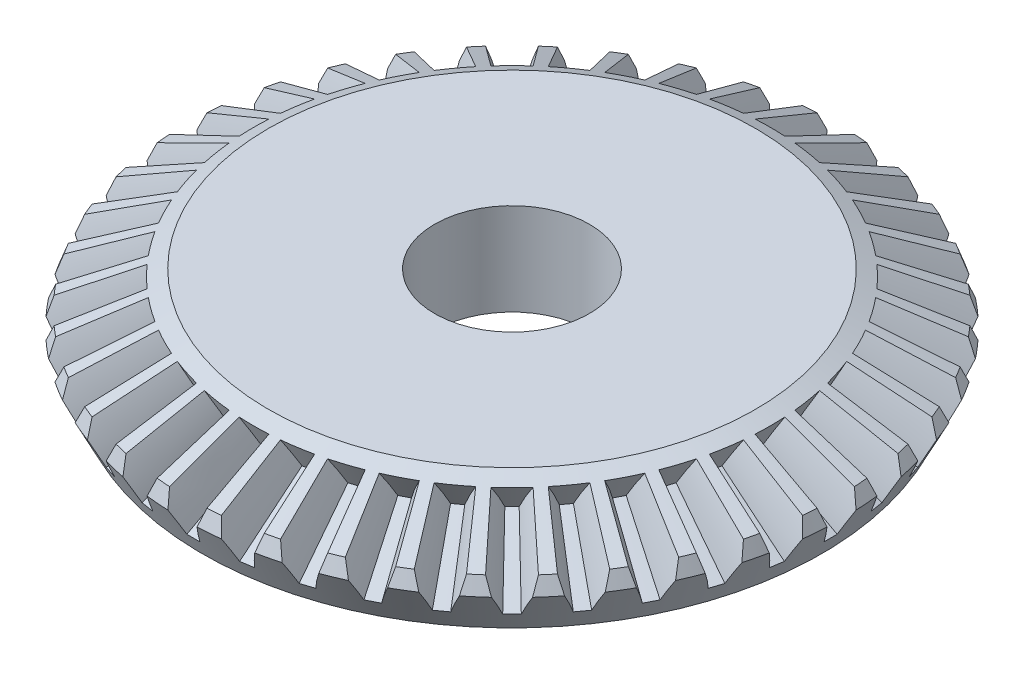
SolidWorks part; units mm, degrees
note: The reader was unsure of these and kept them because the rebuilt part matched: shared geometry of "Section Profile<5>".
ref_plane "Front Plane" through (0, 0, 0) normal (0, 0, 1) x (1, 0, 0)
ref_plane "Top Plane" through (0, 0, 0) normal (0, 1, 0) x (1, 0, 0)
ref_plane "Right Plane" through (0, 0, 0) normal (1, 0, 0) x (0, 0, -1)
ref_plane "Center Plane" through (0, 0, 0) normal (0, 0, 1) x (1, 0, 0)
sketch "Section Profile" plane through (0, 0, 0) normal (0, 0, 1) x (1, 0, 0)
  line L0 (0, 0) -> (0, -63.5) construction
  line L1 (-6, -15.5398) -> (-23.9801, -15.5398)
  line L2 (-23.9801, -15.5398) -> (-25.968, -11.5641)
  line L3 (-25.968, -11.5641) -> (-18.864, -8.4005)
  line L4 (-18.864, -8.4005) -> (-6, -8.4005)
  line L5 (-6, -8.4005) -> (-6, -15.5398)
  line L6 (-25.4, -12.7) -> (-19.5862, -9.7931) construction
  line L7 (-20.0242, -8.9172) -> (-18.9293, -11.107)
  line L8 (-18.9293, -11.107) -> (-24.5481, -14.4039) construction
  line L9 (-18.9293, -11.107) -> (-6, -11.107)
  line L10 (-25.5571, -12.3859) -> (-25.1286, -11.1903)
  line L11 (-25.968, -11.5641) -> (-25.3429, -11.7881) construction
  line L12 (0, 0) -> (-31.75, 0) construction
  dimension "D2" = 6
  dimension "D3" = 1.27
  dimension "D4" = 1.905
  dimension "D6" = 25.4
  dimension "D7" = 1.27
  dimension "D8" = 6.5
  dimension "D9" = 1.27
  dimension "D10" = 1.27
  dimension "D11" = 90
  dimension "D5" = 12.7
revolve "Revolve1" add sketch "Section Profile" angle 360 about L0
ref_plane "Tooth Plane" through (-25.4, -12.7, 0) normal (0.8944, 0.4472, 0) x (-0.4472, 0.8944, 0)
sketch "Tooth Profile" plane through (-25.4, -12.7, 0) normal (0.8944, 0.4472, 0) x (-0.4472, 0.8944, 0)
  line L0 (-56.7961, 0) -> (-3.4257, -0.2154)
  line L1 (-56.7961, 0) -> (-3.4257, 0.2154)
  line L2 (-56.7961, 0) -> (1.27, 0) construction
  line L3 (-0.0088, -0.9974) -> (-56.7961, 0) construction
  line L4 (-56.7961, 0) -> (-0.0088, 0.9974) construction
  circle A0 centre (-56.7961, 0) radius 58.0661 construction
  circle A1 centre (-56.7961, 0) radius 53.3709 construction
  circle A2 centre (-56.7961, 0) radius 56.7961 construction
  arc A3 (1.3762, -1.554) -> (1.3762, 1.554) centre (-56.7961, 0) ccw
  circle A4 centre (-56.7961, 0) radius 55.2086
  spline S0 degree 4 poles (-3.4257, -0.2154) (-3.3862, -0.2155) (-3.2755, -0.2186) (-3.0666, -0.2345) (-2.7269, -0.275) (-2.099, -0.381) (-1.3532, -0.559) (-0.5213, -0.8095) (0.3598, -1.1274) (1.1043, -1.4294) (1.8376, -1.7578) (2.5596, -2.1103) (3.4221, -2.5648) (4.4411, -3.1515) (5.6034, -3.89) (6.8927, -4.7992) (8.1622, -5.7851) (9.3878, -6.824) (10.4229, -7.7768) (11.2824, -8.6199) (11.9826, -9.3425) (12.5292, -9.9263) (13.2058, -10.6779) (13.8538, -11.4281) (14.5026, -12.2204) (15.2306, -13.1426) (15.8643, -13.9908) (16.3987, -14.7279) (17.1314, -15.7961) (17.4562, -16.2884) (17.9484, -17.0504) (18.1922, -17.4486) (18.4082, -17.7948) (18.5072, -17.9626) (18.6069, -18.1262) (18.6477, -18.1948) knots 0 0 0 0 0 0.005377 0.015084 0.028532 0.04661 0.092111 0.119476 0.146842 0.174209 0.201575 0.228941 0.256307 0.307035 0.361767 0.4165 0.471232 0.525964 0.580697 0.608063 0.635429 0.662795 0.690161 0.744894 0.77226 0.799626 0.854358 0.881725 0.909091 0.954545 0.965909 0.977273 0.988636 1 1 1 1 1 construction
  spline S1 degree 4 poles (-3.4257, -0.2154) (-3.3862, -0.2155) (-3.2755, -0.2186) (-3.0666, -0.2345) (-2.7269, -0.275) (-2.099, -0.381) (-1.3532, -0.559) (-0.5213, -0.8095) (0.3598, -1.1274) (1.1043, -1.4294) (1.8376, -1.7578) (2.5596, -2.1103) (3.4221, -2.5648) (4.4411, -3.1515) (5.6034, -3.89) (6.8927, -4.7992) (8.1622, -5.7851) (9.3878, -6.824) (10.4229, -7.7768) (11.2824, -8.6199) (11.9826, -9.3425) (12.5292, -9.9263) (13.2058, -10.6779) (13.8538, -11.4281) (14.5026, -12.2204) (15.2306, -13.1426) (15.8643, -13.9908) (16.3987, -14.7279) (16.9164, -15.4827) (17.1209, -15.7859) (17.2222, -15.9378) knots 0 0 0 0 0 0.005377 0.015084 0.028532 0.04661 0.092111 0.119476 0.146842 0.174209 0.201575 0.228941 0.256307 0.307035 0.361767 0.4165 0.471232 0.525964 0.580697 0.608063 0.635429 0.662795 0.690161 0.744894 0.77226 0.799626 0.854358 0.881725 0.909091 0.909091 0.909091 0.909091 0.909091
  spline S2 degree 4 poles (-3.4257, 0.2154) (-3.3862, 0.2155) (-3.2755, 0.2186) (-3.0666, 0.2345) (-2.7269, 0.275) (-2.099, 0.381) (-1.3532, 0.559) (-0.5213, 0.8095) (0.3598, 1.1274) (1.1043, 1.4294) (1.8376, 1.7578) (2.5596, 2.1103) (3.4221, 2.5648) (4.4411, 3.1515) (5.6034, 3.89) (6.8927, 4.7992) (8.1622, 5.7851) (9.3878, 6.824) (10.4229, 7.7768) (11.2824, 8.6199) (11.9826, 9.3425) (12.5292, 9.9263) (13.2058, 10.6779) (13.8538, 11.4281) (14.5026, 12.2204) (15.2306, 13.1426) (15.8643, 13.9908) (16.3987, 14.7279) (17.1314, 15.7961) (17.4562, 16.2884) (17.9484, 17.0504) (18.1922, 17.4486) (18.4082, 17.7948) (18.5072, 17.9626) (18.6069, 18.1262) (18.6477, 18.1948) knots 0 0 0 0 0 0.005377 0.015084 0.028532 0.04661 0.092111 0.119476 0.146842 0.174209 0.201575 0.228941 0.256307 0.307035 0.361767 0.4165 0.471232 0.525964 0.580697 0.608063 0.635429 0.662795 0.690161 0.744894 0.77226 0.799626 0.854358 0.881725 0.909091 0.954545 0.965909 0.977273 0.988636 1 1 1 1 1 construction
  spline S3 degree 4 poles (-3.4257, 0.2154) (-3.3862, 0.2155) (-3.2755, 0.2186) (-3.0666, 0.2345) (-2.7269, 0.275) (-2.099, 0.381) (-1.3532, 0.559) (-0.5213, 0.8095) (0.3598, 1.1274) (1.1043, 1.4294) (1.8376, 1.7578) (2.5596, 2.1103) (3.4221, 2.5648) (4.4411, 3.1515) (5.6034, 3.89) (6.8927, 4.7992) (8.1622, 5.7851) (9.3878, 6.824) (10.4229, 7.7768) (11.2824, 8.6199) (11.9826, 9.3425) (12.5292, 9.9263) (13.2058, 10.6779) (13.8538, 11.4281) (14.5026, 12.2204) (15.2306, 13.1426) (15.8643, 13.9908) (16.3987, 14.7279) (16.9164, 15.4827) (17.1209, 15.7859) (17.2222, 15.9378) knots 0 0 0 0 0 0.005377 0.015084 0.028532 0.04661 0.092111 0.119476 0.146842 0.174209 0.201575 0.228941 0.256307 0.307035 0.361767 0.4165 0.471232 0.525964 0.580697 0.608063 0.635429 0.662795 0.690161 0.744894 0.77226 0.799626 0.854358 0.881725 0.909091 0.909091 0.909091 0.909091 0.909091
  dimension "D2" = 106.7418
  dimension "D4" = 110.4173
  dimension "D1" = 58.1931
  dimension "D6" = 113.5923
  dimension "D3" = 1.006
  dimension "D5" = 1.006
sketch "Center Point" plane through (0, 0, 0) normal (0, 0, 1) x (1, 0, 0)
  point P0 (0, 0)
loft "Cut-Loft1" cut profiles "Center Point" section "Center Point" section "Tooth Profile"
pattern_circular "CirPattern1" count 40 over 360 about axis through (0, 0, 0) along (0, -1, 0) of "Cut-Loft1"
revolve "Revolve2" add sketch "Section Profile<5>" angle 360 about L0
sketch "Section Profile<5>" plane through (0, 0, 0) normal (0, 0, 1) x (1, 0, 0) same geometry as "Section Profile"
equation "\"Module\"= 1.270mm'20dp = 1.270mod | 32dp = 0.7938mod"
equation "\"Teeth\"= 40"
equation "\"Meshing Teeth\"= 20"
equation "\"Pressure Angle\"= 20deg"
equation "\"Tooth Width\"= 6mm"
equation "\"Tooth Side Clearance\"= 0.5mm"
equation "\"D3@Section Profile\"=\"Module\""
equation "\"D4@Section Profile\"=1.5*\"Module\""
equation "\"D6@Section Profile\"=0.5 * \"Module\" * \"Teeth\""
equation "\"D8@Section Profile\"=\"Tooth Width\" + \"Tooth Side Clearance\""
equation "\"D2@Tooth Profile\" = \"D6@Tooth Profile\" * cos ( \"Pressure Angle\" ) "
equation "\"D3@Tooth Profile\" = 360 /  (  ( \"D6@Tooth Profile\" / \"Module\" )  * 4 ) "
equation "\"D4@Tooth Profile\" = \"D6@Tooth Profile\" -  ( 2 * 1.25 * \"Module\" ) "
equation "\"D1@CirPattern1\"=\"Teeth\""
equation "\"D9@Section Profile\"=\"Module\""
equation "\"D7@Section Profile\"=\"Module\""
equation "\"D1@Tooth Profile\"=( 0.5 * \"D6@Tooth Profile\" )  + ( \"Module\" * 1.1 )"
equation "\"D5@Tooth Profile\"=\"D3@Tooth Profile\""
equation "\"D10@Section Profile\"=\"Module\" * 1.0"
equation "\"Mesh Angle\"= 90deg"
equation "\"D11@Section Profile\"=\"Mesh Angle\""
equation "\"D5@Section Profile\"=0.5 * \"Module\" * \"Meshing Teeth\""
equation "\"D6@Tooth Profile\"=(2*\"D6@Section Profile\")/cos(90-atn(tan(90-\"Mesh Angle\")+(\"D5@Section Profile\"/(\"D6@Section Profile\"*cos(90-\"Mesh Angle\")))))"
